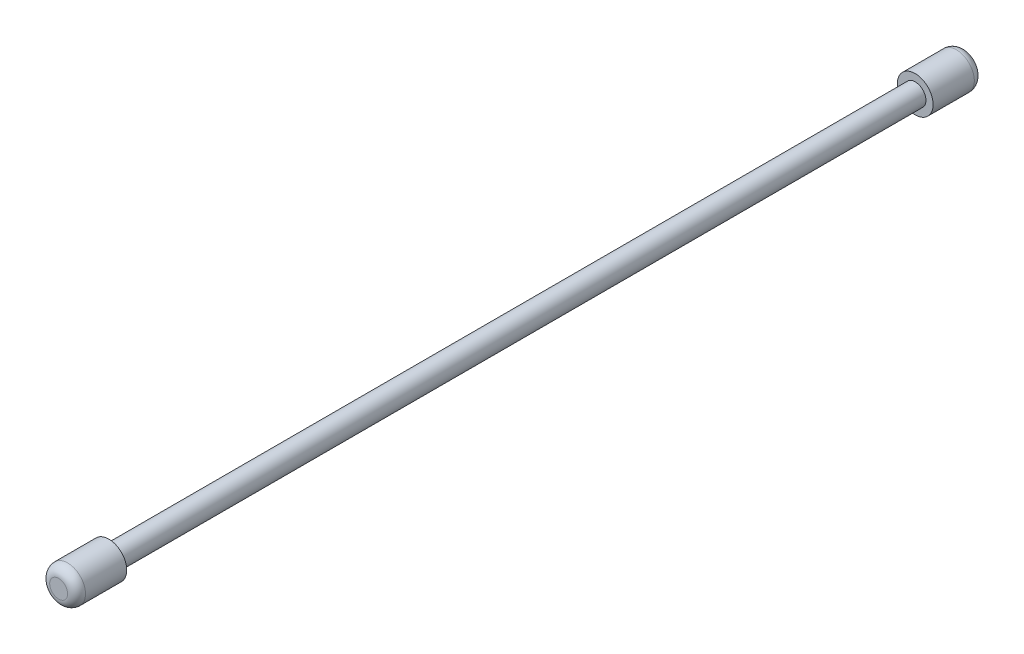
SolidWorks part; units mm, degrees
material "Hexcel AS4C (3000 Filaments)"
ref_plane "Front Plane" through (0, 0, 0) normal (0, 0, 1) x (1, 0, 0)
ref_plane "Top Plane" through (0, 0, 0) normal (0, 1, 0) x (1, 0, 0)
ref_plane "Right Plane" through (0, 0, 0) normal (1, 0, 0) x (0, 0, -1)
sketch "Sketch1" plane through (0, 0, 0) normal (0, 0, 1) x (1, 0, 0)
  circle A0 centre (0, 0) radius 6
  circle A1 centre (0, 0) radius 5
  dimension "D1" = 12
  dimension "D2" = 10
extrude "Boss-Extrude1" add sketch "Sketch1" along normal blind 250 and the other way blind 250
sketch "Sketch2" plane through (0, 0, 250) normal (0, 0, 1) x (1, 0, 0)
  circle A0 centre (0, 0) radius 10
  dimension "D1" = 20
extrude "Boss-Extrude2" add sketch "Sketch2" along normal blind 3 and the other way blind 25
fillet "Fillet1" radius 5 1 edges at (10, 0, 253) type face fillet first side face at (10, 0, 225) second side face at (10, 0, 253)
mirror "Mirror2" about plane through (0, 0, 0) normal (0, 0, 1) of "Boss-Extrude2"
fillet "Fillet2" radius 5 1 edges at (10, 0, -253) type face fillet first side face at (10, 0, -225) second side face at (10, 0, -253)
